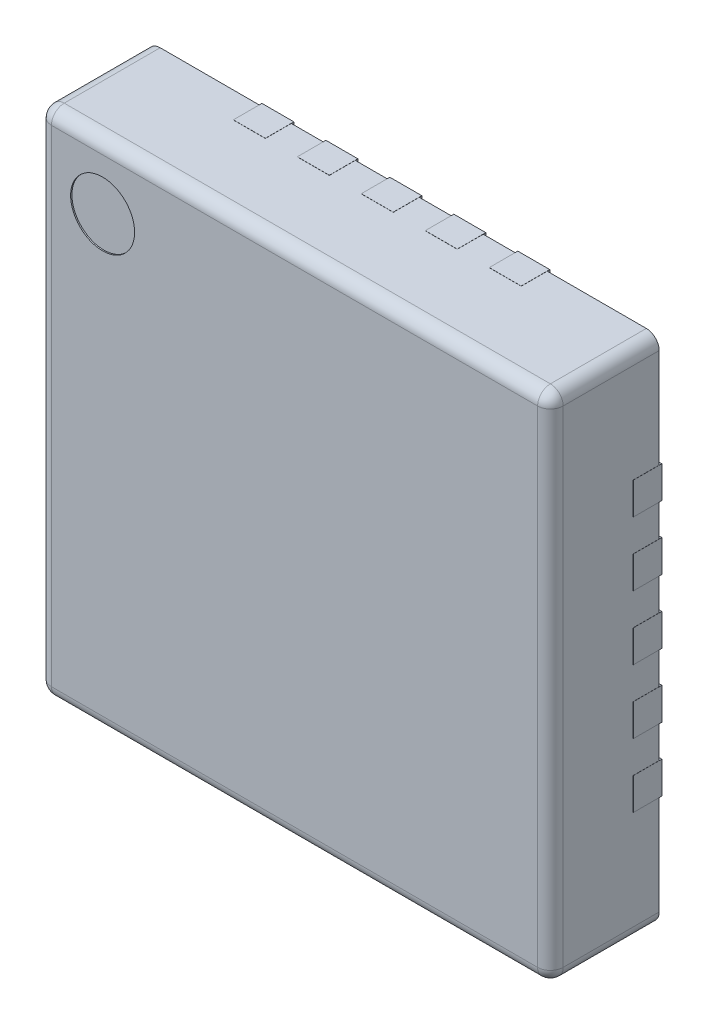
SolidWorks part; units mm, degrees
ref_plane "Front Plane" through (0, 0, 0) normal (0, 0, 1) x (1, 0, 0)
ref_plane "Top Plane" through (0, 0, 0) normal (0, 1, 0) x (1, 0, 0)
ref_plane "Right Plane" through (0, 0, 0) normal (1, 0, 0) x (0, 0, -1)
sketch "Sketch1" plane through (0, 0, 0) normal (0, 0, 1) x (1, 0, 0)
  line L5 (2, -2) -> (-2, -2)
  line L6 (2, -2) -> (2, 2)
  line L7 (2, 2) -> (-2, 2)
  line L8 (-2, -2) -> (-2, 2)
  line L9 (2, -2) -> (-2, 2) construction
  line L10 (2, 2) -> (-2, -2) construction
  point P0 (0, 0)
  dimension "D1" = 4
extrude "Boss-Extrude1" add sketch "Sketch1" along normal blind 0.85
fillet "Fillet1" radius 0.1 8 edges at (-2, -2, 0.425) (-2, 0, 0.85) (0, -2, 0.85) (2, -2, 0.425) (2, 0, 0.85) (0, 2, 0.85) (-2, 2, 0.425) (2, 2, 0.425)
sketch "Sketch2" plane through (0, 0, 0) normal (0, 0, -1) x (-1, 0, 0)
  line L0 (1.2634, 1.0366) -> (1.0366, 1.2634)
  line L1 (0.9482, 1.3) -> (-1.175, 1.3)
  line L2 (1.3, 0.9482) -> (1.3, -1.175)
  line L3 (1.175, -1.3) -> (-1.175, -1.3)
  line L4 (-1.3, 1.175) -> (-1.3, -1.175)
  line L5 (1.3, 1.3) -> (-1.3, -1.3) construction
  line L6 (1.3, -1.3) -> (-1.3, 1.3) construction
  line L7 (-1.9, 2) -> (1.9, 2) construction
  line L8 (-0.125, 2.001) -> (0.125, 2.001)
  line L9 (-0.125, 2.001) -> (-0.125, 1.726)
  line L10 (0, 1.601) -> (0.125, 1.601) construction
  line L11 (0.125, 2.001) -> (0.125, 1.726)
  line L12 (-0.125, 2.001) -> (0.0965, 1.6466) construction
  line L13 (-0.0965, 1.6466) -> (0.125, 2.001) construction
  line L14 (-0.125, 1.601) -> (0, 1.601) construction
  line L15 (-0.125, 1.601) -> (-0.0965, 1.6466) construction
  line L16 (-0.125, 1.726) -> (-0.125, 1.601) construction
  line L17 (0.0965, 1.6466) -> (0.125, 1.601) construction
  line L18 (0.125, 1.726) -> (0.125, 1.601) construction
  line L19 (-0.375, 2.001) -> (-0.375, 1.726)
  line L20 (-0.625, 2.001) -> (-0.625, 1.726)
  line L21 (-0.625, 2.001) -> (-0.375, 2.001)
  line L22 (-0.875, 2.001) -> (-0.875, 1.726)
  line L23 (-1.125, 2.001) -> (-1.125, 1.726)
  line L24 (-1.125, 2.001) -> (-0.875, 2.001)
  line L25 (0, -1000) -> (0, 49000) construction
  line L26 (-1000, 0) -> (49000, 0) construction
  line L27 (1.125, 2.001) -> (0.875, 2.001)
  line L28 (1.125, 2.001) -> (1.125, 1.726)
  line L29 (0.875, 2.001) -> (0.875, 1.726)
  line L30 (0.625, 2.001) -> (0.375, 2.001)
  line L31 (0.625, 2.001) -> (0.625, 1.726)
  line L32 (0.375, 2.001) -> (0.375, 1.726)
  line L33 (1.125, -2.001) -> (1.125, -1.726)
  line L34 (0.875, -2.001) -> (0.875, -1.726)
  line L35 (1.125, -2.001) -> (0.875, -2.001)
  line L36 (0.625, -2.001) -> (0.625, -1.726)
  line L37 (0.375, -2.001) -> (0.375, -1.726)
  line L38 (0.625, -2.001) -> (0.375, -2.001)
  line L39 (-0.125, -2.001) -> (0.125, -2.001)
  line L40 (-0.125, -2.001) -> (-0.125, -1.726)
  line L41 (0.125, -2.001) -> (0.125, -1.726)
  line L42 (-0.625, -2.001) -> (-0.375, -2.001)
  line L43 (-0.625, -2.001) -> (-0.625, -1.726)
  line L44 (-0.375, -2.001) -> (-0.375, -1.726)
  line L45 (-1.125, -2.001) -> (-0.875, -2.001)
  line L46 (-1.125, -2.001) -> (-1.125, -1.726)
  line L47 (-0.875, -2.001) -> (-0.875, -1.726)
  line L48 (2.001, -1.125) -> (2.001, -0.875)
  line L49 (2.001, -0.875) -> (1.726, -0.875)
  line L50 (2.001, -1.125) -> (1.726, -1.125)
  line L51 (2.001, -0.625) -> (2.001, -0.375)
  line L52 (2.001, -0.375) -> (1.726, -0.375)
  line L53 (2.001, -0.625) -> (1.726, -0.625)
  line L54 (2.001, 0.125) -> (1.726, 0.125)
  line L55 (2.001, -0.125) -> (1.726, -0.125)
  line L56 (2.001, 0.125) -> (2.001, -0.125)
  line L57 (2.001, 0.625) -> (1.726, 0.625)
  line L58 (2.001, 0.375) -> (1.726, 0.375)
  line L59 (2.001, 0.625) -> (2.001, 0.375)
  line L60 (2.001, 1.125) -> (1.726, 1.125)
  line L61 (2.001, 0.875) -> (1.726, 0.875)
  line L62 (2.001, 1.125) -> (2.001, 0.875)
  line L63 (-2.001, -1.125) -> (-1.726, -1.125)
  line L64 (-2.001, -0.875) -> (-1.726, -0.875)
  line L65 (-2.001, -1.125) -> (-2.001, -0.875)
  line L66 (-2.001, -0.625) -> (-1.726, -0.625)
  line L67 (-2.001, -0.375) -> (-1.726, -0.375)
  line L68 (-2.001, -0.625) -> (-2.001, -0.375)
  line L69 (-2.001, 0.125) -> (-2.001, -0.125)
  line L70 (-2.001, 0.125) -> (-1.726, 0.125)
  line L71 (-2.001, -0.125) -> (-1.726, -0.125)
  line L72 (-2.001, 0.625) -> (-2.001, 0.375)
  line L73 (-2.001, 0.625) -> (-1.726, 0.625)
  line L74 (-2.001, 0.375) -> (-1.726, 0.375)
  line L75 (-2.001, 1.125) -> (-2.001, 0.875)
  line L76 (-2.001, 1.125) -> (-1.726, 1.125)
  line L77 (-2.001, 0.875) -> (-1.726, 0.875)
  arc A0 (-0.125, 1.726) -> (0.125, 1.726) centre (0, 1.726) ccw
  arc A1 (-0.625, 1.726) -> (-0.375, 1.726) centre (-0.5, 1.726) ccw
  arc A2 (-1.125, 1.726) -> (-0.875, 1.726) centre (-1, 1.726) ccw
  arc A3 (1.125, 1.726) -> (0.875, 1.726) centre (1, 1.726) cw
  arc A4 (0.625, 1.726) -> (0.375, 1.726) centre (0.5, 1.726) cw
  arc A5 (1.125, -1.726) -> (0.875, -1.726) centre (1, -1.726) ccw
  arc A6 (0.625, -1.726) -> (0.375, -1.726) centre (0.5, -1.726) ccw
  arc A7 (-0.125, -1.726) -> (0.125, -1.726) centre (0, -1.726) cw
  arc A8 (-0.625, -1.726) -> (-0.375, -1.726) centre (-0.5, -1.726) cw
  arc A9 (-1.125, -1.726) -> (-0.875, -1.726) centre (-1, -1.726) cw
  arc A10 (1.726, -1.125) -> (1.726, -0.875) centre (1.726, -1) cw
  arc A11 (1.726, -0.625) -> (1.726, -0.375) centre (1.726, -0.5) cw
  arc A12 (1.726, 0.125) -> (1.726, -0.125) centre (1.726, 0) ccw
  arc A13 (1.726, 0.625) -> (1.726, 0.375) centre (1.726, 0.5) ccw
  arc A14 (1.726, 1.125) -> (1.726, 0.875) centre (1.726, 1) ccw
  arc A15 (-1.726, -1.125) -> (-1.726, -0.875) centre (-1.726, -1) ccw
  arc A16 (-1.726, -0.625) -> (-1.726, -0.375) centre (-1.726, -0.5) ccw
  arc A17 (-1.726, 0.125) -> (-1.726, -0.125) centre (-1.726, 0) cw
  arc A18 (-1.726, 0.625) -> (-1.726, 0.375) centre (-1.726, 0.5) cw
  arc A19 (-1.726, 1.125) -> (-1.726, 0.875) centre (-1.726, 1) cw
  arc A20 (1.3, -1.175) -> (1.175, -1.3) centre (1.175, -1.175) cw
  arc A21 (-1.175, -1.3) -> (-1.3, -1.175) centre (-1.175, -1.175) cw
  arc A22 (1.2634, 1.0366) -> (1.3, 0.9482) centre (1.175, 0.9482) cw
  arc A23 (1.0366, 1.2634) -> (0.9482, 1.3) centre (0.9482, 1.175) ccw
  arc A24 (-1.175, 1.3) -> (-1.3, 1.175) centre (-1.175, 1.175) ccw
  point P0 (0, 0)
  point P8 (0, 1.801)
  point P130 (1, 1.3)
  dimension "D8" = 3
  dimension "D10" = 0.125
  dimension "D11" = 0.125
  dimension "D12" = 0.125
  dimension "D13" = 0.125
  dimension "D14" = 0.125
  dimension "D1" = 2.6
  dimension "D2" = 0.3
  dimension "D3" = 45
  dimension "D4" = 2.6
  dimension "D5" = 0.001
  dimension "D6" = 0.4
  dimension "D7" = 0.25
  dimension "D9" = 0.5
extrude "Boss-Extrude2" add sketch "Sketch2" along normal blind 0.02 and the other way blind 0.203 separate body
sketch "Sketch3" plane through (0, 0, 0.85) normal (0, 0, 1) x (1, 0, 0)
  line L0 (2, 2) -> (-2, 2) construction
  line L1 (-2, 2) -> (-2, -2) construction
  circle A0 centre (-1.5, 1.5) radius 0.25
  dimension "D1" = 0.5
  dimension "D2" = 0.5
  dimension "D3" = 0.5
extrude "Cut-Extrude1" cut sketch "Sketch3" against normal blind 0.01
